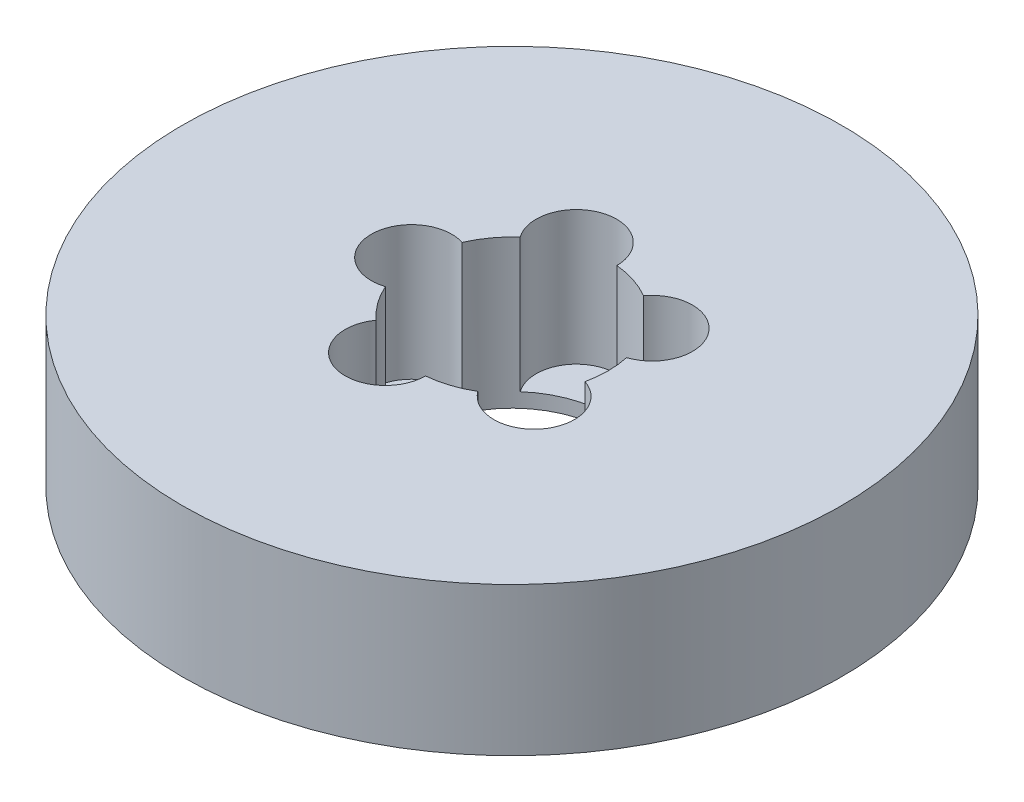
SolidWorks part; units mm, degrees
ref_plane "Front Plane" through (0, 0, 0) normal (0, 0, 1) x (1, 0, 0)
ref_plane "Top Plane" through (0, 0, 0) normal (0, 1, 0) x (1, 0, 0)
ref_plane "Right Plane" through (0, 0, 0) normal (1, 0, 0) x (0, 0, -1)
sketch "Sketch1" plane through (0, 0, 0) normal (0, 1, 0) x (1, 0, 0)
  circle A0 centre (0, 0) radius 60
  dimension "FLANGE_OD" = 120
extrude "Boss-Extrude1" add sketch "Sketch1" along normal blind 27
sketch "Sketch2" plane through (0, 0, 0) normal (0, 1, 0) x (1, 0, 0)
  circle A0 centre (0, 0) radius 17.5
  dimension "BORE_D" = 35
extrude "Cut-Extrude1" cut sketch "Sketch2" along normal through all
sketch "Sketch3" plane through (0, 27, 0) normal (0, 1, 0) x (1, 0, 0)
  circle A0 centre (0, 0) radius 18.2758 construction
  circle A1 centre (-18.2758, 0) radius 7.3301
  dimension "BOLT_D" = 14.6603
  dimension "BOLT_PCD" = 36.5517
extrude "Cut-Extrude2" cut sketch "Sketch3" against normal blind 24.3801
pattern_circular "CirPattern1" count 5 over 360 about axis through (0, 0, 0) along (0, 1, 0) of "Cut-Extrude2"
